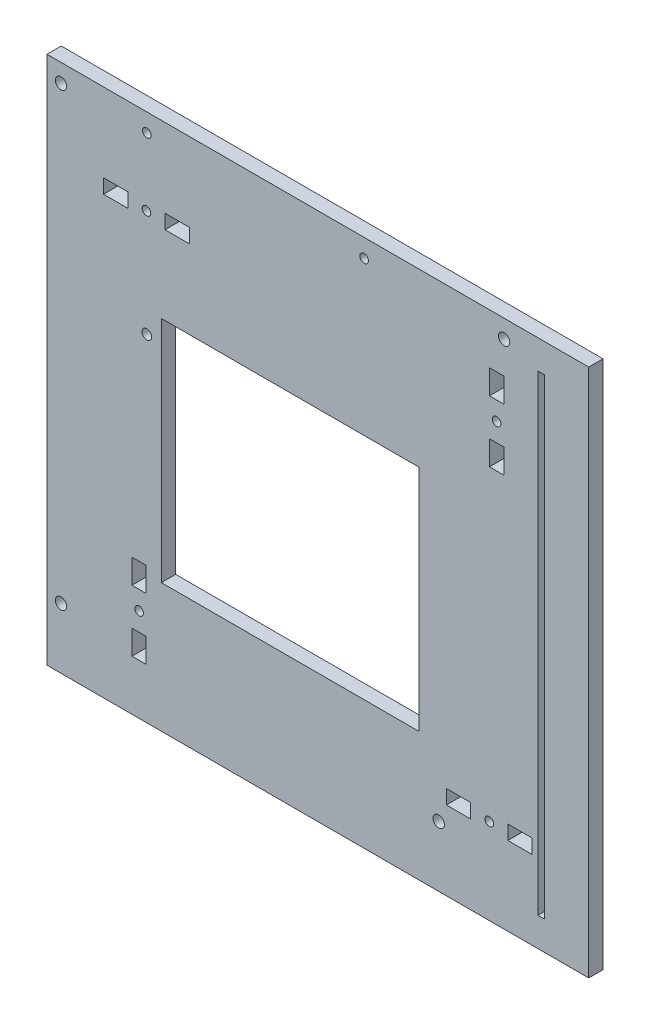
SolidWorks part; units mm, degrees
ref_plane "Front Plane" through (0, 0, 0) normal (0, 0, 1) x (1, 0, 0)
ref_plane "Top Plane" through (0, 0, 0) normal (0, 1, 0) x (1, 0, 0)
ref_plane "Right Plane" through (0, 0, 0) normal (1, 0, 0) x (0, 0, -1)
sketch "Sketch2" plane through (0, 0, 0) normal (0, 0, 1) x (1, 0, 0)
  line L0 (104.43, 85) -> (-85, -100) construction
  line L1 (-85, 85) -> (104.43, 85)
  line L2 (-85, 85) -> (-85, -100)
  line L3 (-85, -100) -> (104.43, -100)
  line L4 (104.43, 85) -> (104.43, -100)
  line L5 (96.43, 71.875) -> (96.43, 85) construction
  line L6 (88.43, -89.415) -> (87.11, -89.415) construction
  line L7 (96.43, -86.875) -> (96.43, -100) construction
  line L8 (88.43, 73.415) -> (88.43, -88.415) construction
  line L9 (87.11, -89.415) -> (87.11, 73.415) construction
  line L10 (88.43, 74.415) -> (87.11, 74.415) construction
  line L11 (-80.1, 78.65) -> (51.98, 78.65) construction
  line L12 (-80.1, 78.65) -> (-80.1, -78.83) construction
  line L13 (-80.1, -78.83) -> (51.98, -78.83) construction
  line L14 (51.98, 78.65) -> (51.98, -78.83) construction
  line L15 (74.84, 78.65) -> (-80.1, 78.65) construction
  line L16 (74.84, 78.65) -> (74.84, -78.83) construction
  line L17 (74.84, -78.83) -> (-80.1, -78.83) construction
  line L18 (-80.1, 78.65) -> (-80.1, -78.83) construction
  line L19 (88.93, -89.915) -> (86.61, -89.915)
  line L20 (88.93, -89.915) -> (88.93, 74.915)
  line L21 (88.93, 74.915) -> (86.61, 74.915)
  line L22 (86.61, -89.915) -> (86.61, 74.915)
  line L23 (88.93, -89.915) -> (86.61, 74.915) construction
  line L24 (88.93, 74.915) -> (86.61, -89.915) construction
  line L25 (-56.7109, 57.5) -> (-65.2109, 57.5)
  line L26 (25.9, 78.65) -> (-50.1, 78.65) construction
  line L27 (45, -55) -> (-45, -55)
  line L28 (45, -55) -> (45, 25)
  line L29 (45, 25) -> (-45, 25)
  line L30 (-45, -55) -> (-45, 25)
  line L31 (45, -55) -> (-45, 25) construction
  line L32 (45, 25) -> (-45, -55) construction
  line L33 (25.9, 78.65) -> (25.9, 17.65) construction
  line L34 (25.9, 17.65) -> (-50.1, 17.65) construction
  line L35 (-50.1, 78.65) -> (-50.1, 17.65) construction
  line L36 (-35.2109, 52.5) -> (-43.7109, 52.5)
  line L37 (-35.2109, 52.5) -> (-35.2109, 57.5)
  line L38 (-35.2109, 57.5) -> (-43.7109, 57.5)
  line L39 (-65.2109, 52.5) -> (-65.2109, 57.5)
  line L40 (-43.7109, 55) -> (-56.7109, 55) construction
  line L41 (-43.7109, 52.5) -> (-43.7109, 57.5)
  line L42 (74.715, 58.9259) -> (74.715, 67.4259)
  line L43 (-56.7109, 52.5) -> (-56.7109, 57.5)
  line L44 (-56.7109, 52.5) -> (-65.2109, 52.5)
  line L45 (69.715, 37.4259) -> (69.715, 45.9259)
  line L46 (69.715, 37.4259) -> (74.715, 37.4259)
  line L47 (74.715, 37.4259) -> (74.715, 45.9259)
  line L48 (69.715, 67.4259) -> (74.715, 67.4259)
  line L49 (69.715, 45.9259) -> (74.715, 45.9259)
  line L50 (69.715, 58.9259) -> (74.715, 58.9259)
  line L51 (69.715, 58.9259) -> (69.715, 67.4259)
  line L52 (72.215, 45.9259) -> (72.215, 58.9259) construction
  line L53 (76.1409, -72.5) -> (84.6409, -72.5)
  line L54 (54.6409, -67.5) -> (63.1409, -67.5)
  line L55 (54.6409, -67.5) -> (54.6409, -72.5)
  line L56 (54.6409, -72.5) -> (63.1409, -72.5)
  line L57 (84.6409, -67.5) -> (84.6409, -72.5)
  line L58 (63.1409, -67.5) -> (63.1409, -72.5)
  line L59 (76.1409, -67.5) -> (76.1409, -72.5)
  line L60 (76.1409, -67.5) -> (84.6409, -67.5)
  line L61 (63.1409, -70) -> (76.1409, -70) construction
  line L62 (-55.285, -73.9259) -> (-55.285, -82.4259)
  line L63 (-50.285, -52.4259) -> (-50.285, -60.9259)
  line L64 (-50.285, -52.4259) -> (-55.285, -52.4259)
  line L65 (-55.285, -52.4259) -> (-55.285, -60.9259)
  line L66 (-50.285, -82.4259) -> (-55.285, -82.4259)
  line L67 (-50.285, -60.9259) -> (-55.285, -60.9259)
  line L68 (-50.285, -73.9259) -> (-55.285, -73.9259)
  line L69 (-50.285, -73.9259) -> (-50.285, -82.4259)
  line L70 (-52.785, -60.9259) -> (-52.785, -73.9259) construction
  line L71 (74.715, 67.4259) -> (69.715, 67.4259) construction
  line L72 (69.715, 67.4259) -> (69.715, 58.9259) construction
  circle A0 centre (-80.1, 78.65) radius 1.98
  circle A1 centre (74.84, 78.65) radius 1.98
  circle A2 centre (51.98, -78.83) radius 1.98
  circle A3 centre (-80.1, -78.83) radius 1.98
  circle A4 centre (25.9, 78.65) radius 1.5
  circle A5 centre (-50.1, 78.65) radius 1.5
  circle A6 centre (-50.1, 17.65) radius 1.6948
  circle A7 centre (-50.2109, 55) radius 1.5
  circle A8 centre (72.215, 52.4259) radius 1.5
  circle A9 centre (69.6409, -70) radius 1.5
  circle A10 centre (-52.785, -67.4259) radius 1.5
  circle A11 centre (9.715, -7.5) radius 132.3903 construction
  point P8 (0, -15)
  point P28 (87.77, -7.5)
  dimension "D8" = 3
  dimension "D1" = 0.5
  dimension "D2" = 0.5
  dimension "D3" = 0.5
  dimension "D4" = 0.5
  dimension "D5" = 76
  dimension "D6" = 61
  dimension "D7" = 30
  dimension "D9" = 4
extrude "Boss-Extrude1" add sketch "Sketch2" along normal blind 5
